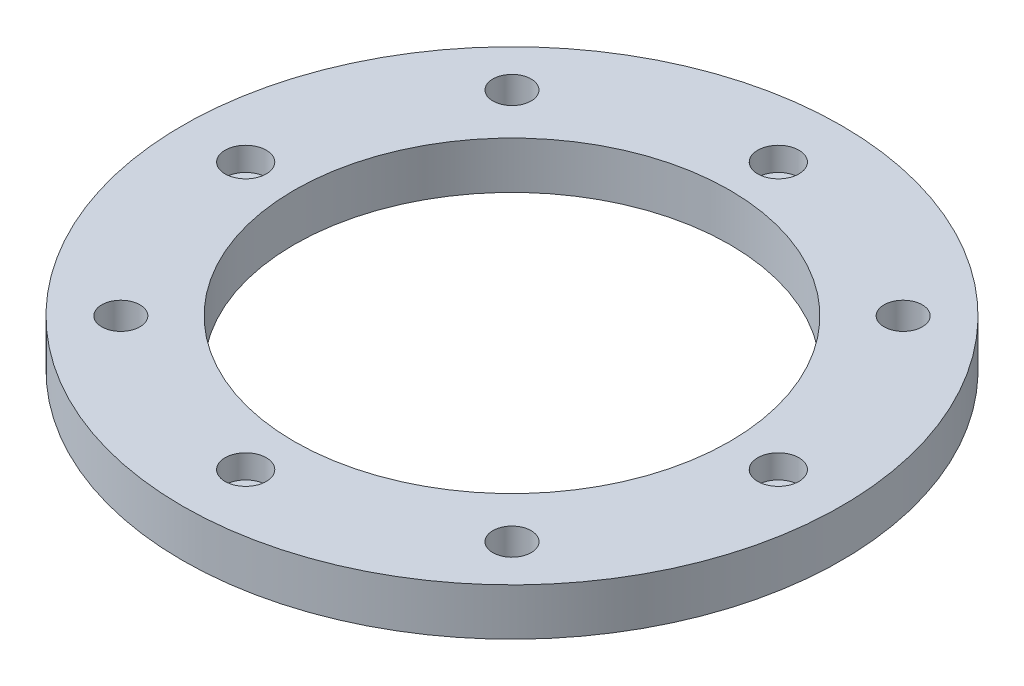
SolidWorks part; units mm, degrees
material "6061 Alloy"
ref_plane "Front Plane" through (0, 0, 0) normal (0, 0, 1) x (1, 0, 0)
ref_plane "Top Plane" through (0, 0, 0) normal (0, 1, 0) x (1, 0, 0)
ref_plane "Right Plane" through (0, 0, 0) normal (1, 0, 0) x (0, 0, -1)
sketch "Sketch1" plane through (0, 0, 0) normal (0, 1, 0) x (1, 0, 0)
  line L1 (-88.9, -88.9) -> (88.9, -88.9)
  line L2 (-88.9, -88.9) -> (-88.9, 88.9)
  line L3 (-88.9, 88.9) -> (88.9, 88.9)
  line L4 (88.9, -88.9) -> (88.9, 88.9)
  line L5 (-88.9, -88.9) -> (88.9, 88.9) construction
  line L6 (-88.9, 88.9) -> (88.9, -88.9) construction
  point P0 (0, 0)
  dimension "D1" = 177.8
extrude "Boss-Extrude1" add sketch "Sketch1" along normal blind 12.7
sketch "Sketch2" plane through (0, 12.7, 0) normal (0, 1, 0) x (1, 0, 0)
  line L1 (-52.759, -52.759) -> (52.759, -52.759) construction
  line L2 (-52.759, -52.759) -> (-52.759, 52.759) construction
  line L3 (-52.759, 52.759) -> (52.759, 52.759) construction
  line L4 (52.759, -52.759) -> (52.759, 52.759) construction
  line L5 (-52.759, -52.759) -> (52.759, 52.759) construction
  line L6 (-52.759, 52.759) -> (52.759, -52.759) construction
  circle A0 centre (0, 0) radius 74.6125 construction
  point P3 (-52.759, 52.759)
  point P4 (52.759, 52.759)
  point P5 (52.759, -52.759)
  point P6 (-52.759, -52.759)
  dimension "D1" = 149.225
hole_wizard "13/32 (0.40625) Diameter Hole1" positions "3DSketch1" profile "Sketch3" hole size "13/32" standard "ANSI Inch" end condition through all
sketch3d "3DSketch1"
  point P0 (-52.759, 12.7, -52.759)
  point P3 (52.759, 12.7, -52.759)
  point P6 (52.759, 12.7, 52.759)
  point P9 (-52.759, 12.7, 52.759)
sketch "Sketch3" plane through (-52.759, 12.7, -52.759) normal (1, 0, 0) x (0, 0, 1)
  line L0 (0, 0) -> (0, 12.7)
  line L1 (0, 12.7) -> (5.1594, 12.7)
  line L2 (5.1594, 12.7) -> (5.1594, 0)
  line L5 (5.1594, 0) -> (0, 0)
  line L11 (0, -6.35) -> (0, 107.95) construction
  dimension "Thru Hole Dia." = 10.3187
  dimension "Thru Hole Depth" = 12.7
sketch "Sketch4" plane through (0, 12.7, 0) normal (0, 1, 0) x (1, 0, 0)
  circle A0 centre (0, 0) radius 58.7375
  dimension "D1" = 117.475
extrude "Cut-Extrude1" cut sketch "Sketch4" against normal through all
sketch "Sketch5" plane through (0, 12.7, 0) normal (0, 1, 0) x (1, 0, 0)
  line L0 (88.9, 88.9) -> (-88.9, 88.9) construction
  circle A0 centre (0, 0) radius 88.9
extrude "Cut-Extrude2" cut sketch "Sketch5" against normal blind 12.7 flip side to cut
sketch "Sketch6" plane through (0, 12.7, 0) normal (0, 1, 0) x (1, 0, 0)
  line L0 (-71.842, 0) -> (0, 0) construction
  line L1 (0, 0) -> (71.842, 0) construction
  line L2 (71.842, 0) -> (0, 71.842) construction
  line L3 (0, 71.842) -> (0, 0) construction
  line L4 (0, 0) -> (0, -71.842) construction
  point P0 (0, 71.842)
  point P1 (71.842, 0)
  point P4 (-71.842, 0)
  point P5 (0, -71.842)
  dimension "D2" = 101.6
hole_wizard "CBORE for 1/4 Socket Head Cap Screw1" positions "3DSketch2" profile "Sketch9" counterbore size "1/4" standard "ANSI Inch" end condition through all
sketch3d "3DSketch2"
  point P0 (0, 12.7, -71.842)
  point P3 (71.842, 12.7, 0)
  point P6 (-71.842, 12.7, 0)
  point P9 (0, 12.7, 71.842)
sketch "Sketch9" plane through (0, 12.7, -71.842) normal (1, 0, 0) x (0, 0, 1)
  line L0 (0, 0) -> (0, 12.7)
  line L1 (0, 12.7) -> (3.3782, 12.7)
  line L3 (3.3782, 12.7) -> (3.3782, 6.35)
  line L4 (3.3782, 6.35) -> (5.5562, 6.35)
  line L5 (5.5562, 6.35) -> (5.5562, 0)
  line L7 (5.5562, 0) -> (0, 0)
  line L11 (0, -6.35) -> (0, 107.95) construction
  dimension "Thru Hole Dia." = 6.7564
  dimension "Thru Hole Depth" = 12.7
  dimension "C'Bore Dia." = 11.1125
  dimension "C'Bore Depth" = 6.35
